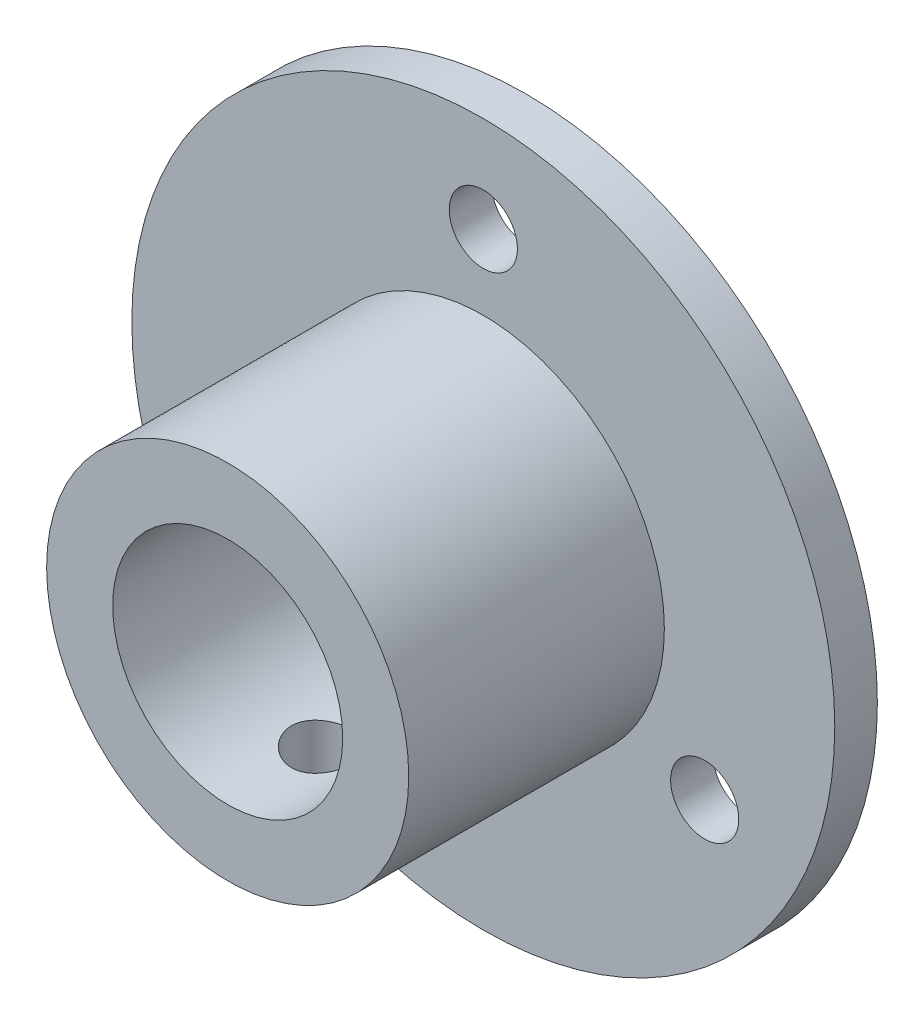
SolidWorks part; units mm, degrees
ref_plane "前视基准面" through (0, 0, 0) normal (0, 0, 1) x (1, 0, 0)
ref_plane "上视基准面" through (0, 0, 0) normal (0, 1, 0) x (1, 0, 0)
ref_plane "右视基准面" through (0, 0, 0) normal (1, 0, 0) x (0, 0, -1)
sketch "草图1" plane through (0, 0, 0) normal (0, 0, 1) x (1, 0, 0)
  circle A0 centre (0, 0) radius 16.5
extrude "凸台-拉伸1" add sketch "草图1" along normal blind 2
sketch "草图2" plane through (0, 0, 2) normal (0, 0, 1) x (1, 0, 0)
  circle A0 centre (0, 0) radius 8.5
extrude "凸台-拉伸2" add sketch "草图2" along normal blind 12
sketch "草图3" plane through (0, 0, 14) normal (0, 0, 1) x (1, 0, 0)
  circle A0 centre (0, 0) radius 5.4
extrude "切除-拉伸1" cut sketch "草图3" against normal blind 29
sketch "草图4" plane through (0, 0, 0) normal (0, 0, -1) x (-1, 0, 0)
  circle A1 centre (0, 12) radius 1.6
  circle A2 centre (0, 0) radius 12 construction
  circle A3 centre (10.3923, -6) radius 1.6
  circle A4 centre (-10.3923, -6) radius 1.6
  point P13 (0, 0)
  point P15 (0, 0)
  point P17 (0, 0)
  dimension "D1" = 3
extrude "切除-拉伸2" cut sketch "草图4" against normal blind 29
ref_axis "基准轴1" through (0, 0, -16.9963) along (0, 0, 1)
sketch "草图7" plane through (0, 0, 0) normal (0, 1, 0) x (1, 0, 0)
  line L0 (0, -14) -> (0, -9.5)
  line L1 (-8.5, -14) -> (8.5, -14) construction
  line L2 (0, 16.9963) -> (0, -25.3718) construction
  circle A0 centre (0, -9.5) radius 1.5
extrude "切除-拉伸3" cut sketch "草图7" against normal blind 12 contours A0 region at (1.0307, 0, 10.5307)
